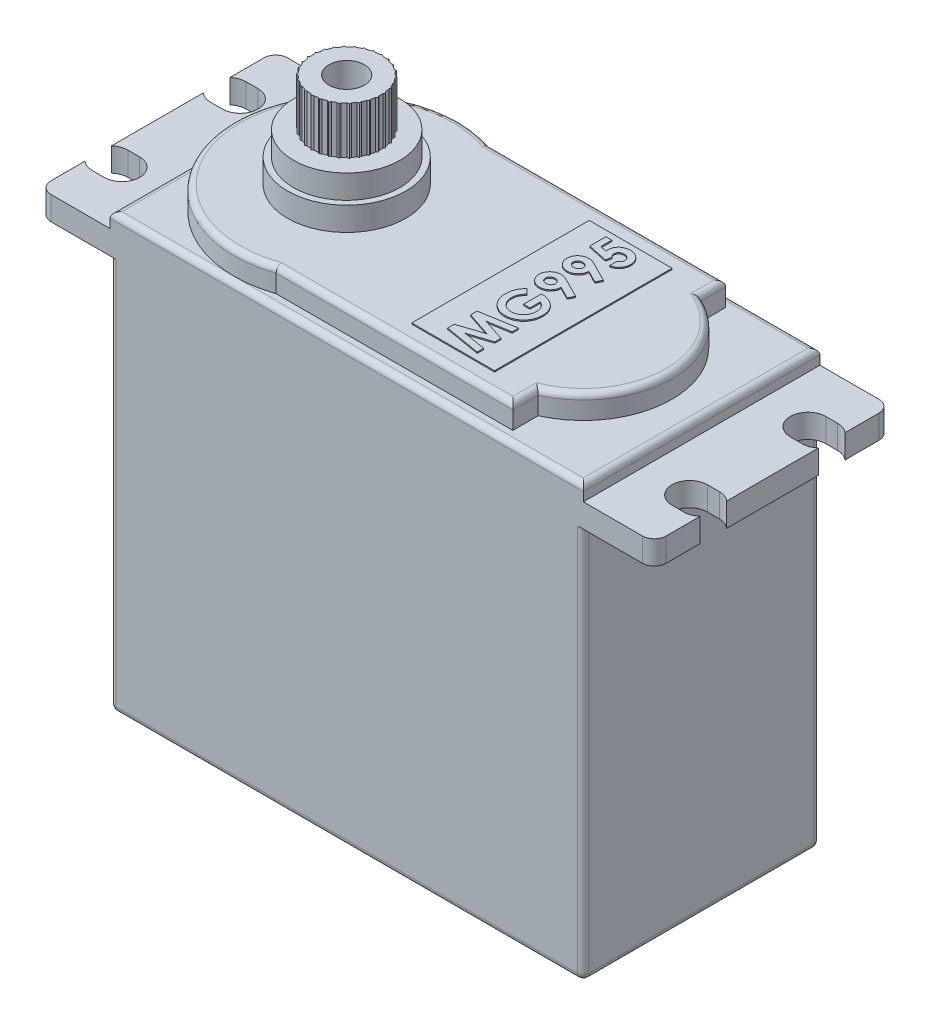
SolidWorks part; units mm, degrees
ref_plane "Front Plane" through (0, 0, 0) normal (0, 0, 1) x (1, 0, 0)
ref_plane "Top Plane" through (0, 0, 0) normal (0, 1, 0) x (1, 0, 0)
ref_plane "Right Plane" through (0, 0, 0) normal (1, 0, 0) x (0, 0, -1)
sketch "Sketch1" plane through (0, 0, 0) normal (0, 1, 0) x (1, 0, 0)
  line L1 (-20, 10) -> (20, 10)
  line L2 (-20, 10) -> (-20, -10)
  line L3 (-20, -10) -> (20, -10)
  line L4 (20, 10) -> (20, -10)
  line L5 (-20, 10) -> (20, -10) construction
  line L6 (-20, -10) -> (20, 10) construction
  point P0 (0, 0)
  dimension "D1" = 20
  dimension "D2" = 40
extrude "Extrude1" add sketch "Sketch1" along normal mid plane 36.5
sketch "Sketch2" plane through (0, 18.25, 0) normal (0, 1, 0) x (1, 0, 0)
  line L0 (13.0414, -6.8557) -> (13.0414, -9)
  line L1 (-6.9586, 9) -> (13.0414, 9)
  line L3 (-6.9586, -9) -> (13.0414, -9)
  line L4 (13.0414, 9) -> (13.0414, 6.8557)
  arc A0 (-6.9586, 9) -> (-6.9586, -9) centre (-10, 0) ccw
  arc A1 (13.0414, -6.8557) -> (13.0414, 6.8557) centre (10, 0) ccw
  dimension "D1" = 19
  dimension "D4" = 15
  dimension "D2" = 10
  dimension "D3" = 18
  dimension "D5" = 20
  dimension "D6" = 10
extrude "Extrude2" add sketch "Sketch2" along normal blind 2
sketch "Sketch3" plane through (0, 20.25, 0) normal (0, 1, 0) x (1, 0, 0)
  circle A0 centre (-10, 0) radius 5
  dimension "D1" = 10
extrude "Extrude3" add sketch "Sketch3" along normal blind 2
sketch "Sketch4" plane through (0, 22.25, 0) normal (0, 1, 0) x (1, 0, 0)
  circle A0 centre (-10, 0) radius 4.5
  dimension "D1" = 9
extrude "Extrude4" add sketch "Sketch4" along normal blind 2
sketch "Sketch5" plane through (0, 24.25, 0) normal (0, 1, 0) x (1, 0, 0)
  line L0 (-10, 0) -> (-10, 3) construction
  line L1 (-10, 3) -> (-10.125, 2.8973)
  line L2 (-10, 3) -> (-9.875, 2.8973)
  line L3 (-9.3763, 2.9344) -> (-9.5199, 2.86)
  line L4 (-9.3763, 2.9344) -> (-9.2753, 2.808)
  line L5 (-8.7798, 2.7406) -> (-8.9358, 2.6977)
  line L6 (-8.7798, 2.7406) -> (-8.7074, 2.596)
  line L7 (-8.2366, 2.4271) -> (-8.3981, 2.4174)
  line L8 (-8.2366, 2.4271) -> (-8.1959, 2.2705)
  line L9 (-7.7706, 2.0074) -> (-7.9305, 2.0316)
  line L10 (-7.7706, 2.0074) -> (-7.7632, 1.8458)
  line L11 (-7.4019, 1.5) -> (-7.5534, 1.5569)
  line L12 (-7.4019, 1.5) -> (-7.4284, 1.3404)
  line L13 (-7.1468, 0.9271) -> (-7.2831, 1.0142)
  line L14 (-7.1468, 0.9271) -> (-7.2059, 0.7764)
  line L15 (-7.0164, 0.3136) -> (-7.1316, 0.4272)
  line L16 (-7.0164, 0.3136) -> (-7.1055, 0.1785)
  line L17 (-7.0164, -0.3136) -> (-7.1055, -0.1785)
  line L18 (-7.0164, -0.3136) -> (-7.1316, -0.4272)
  line L19 (-7.1468, -0.9271) -> (-7.2059, -0.7764)
  line L20 (-7.1468, -0.9271) -> (-7.2831, -1.0142)
  line L21 (-7.4019, -1.5) -> (-7.4284, -1.3404)
  line L22 (-7.4019, -1.5) -> (-7.5534, -1.5569)
  line L23 (-7.7706, -2.0074) -> (-7.7632, -1.8458)
  line L24 (-7.7706, -2.0074) -> (-7.9305, -2.0316)
  line L25 (-8.2366, -2.4271) -> (-8.1959, -2.2705)
  line L26 (-8.2366, -2.4271) -> (-8.3981, -2.4174)
  line L27 (-8.7798, -2.7406) -> (-8.7074, -2.596)
  line L28 (-8.7798, -2.7406) -> (-8.9358, -2.6977)
  line L29 (-9.3763, -2.9344) -> (-9.2753, -2.808)
  line L30 (-9.3763, -2.9344) -> (-9.5199, -2.86)
  line L31 (-10, -3) -> (-9.875, -2.8973)
  line L32 (-10, -3) -> (-10.125, -2.8973)
  line L33 (-10.6237, -2.9344) -> (-10.4801, -2.86)
  line L34 (-10.6237, -2.9344) -> (-10.7247, -2.808)
  line L35 (-11.2202, -2.7406) -> (-11.0642, -2.6977)
  line L36 (-11.2202, -2.7406) -> (-11.2926, -2.596)
  line L37 (-11.7634, -2.4271) -> (-11.6019, -2.4174)
  line L38 (-11.7634, -2.4271) -> (-11.8041, -2.2705)
  line L39 (-12.2294, -2.0074) -> (-12.0695, -2.0316)
  line L40 (-12.2294, -2.0074) -> (-12.2368, -1.8458)
  line L41 (-12.5981, -1.5) -> (-12.4466, -1.5569)
  line L42 (-12.5981, -1.5) -> (-12.5716, -1.3404)
  line L43 (-12.8532, -0.9271) -> (-12.7169, -1.0142)
  line L44 (-12.8532, -0.9271) -> (-12.7941, -0.7764)
  line L45 (-12.9836, -0.3136) -> (-12.8684, -0.4272)
  line L46 (-12.9836, -0.3136) -> (-12.8945, -0.1785)
  line L47 (-12.9836, 0.3136) -> (-12.8945, 0.1785)
  line L48 (-12.9836, 0.3136) -> (-12.8684, 0.4272)
  line L49 (-12.8532, 0.9271) -> (-12.7941, 0.7764)
  line L50 (-12.8532, 0.9271) -> (-12.7169, 1.0142)
  line L51 (-12.5981, 1.5) -> (-12.5716, 1.3404)
  line L52 (-12.5981, 1.5) -> (-12.4466, 1.5569)
  line L53 (-12.2294, 2.0074) -> (-12.2368, 1.8458)
  line L54 (-12.2294, 2.0074) -> (-12.0695, 2.0316)
  line L55 (-11.7634, 2.4271) -> (-11.8041, 2.2705)
  line L56 (-11.7634, 2.4271) -> (-11.6019, 2.4174)
  line L57 (-11.2202, 2.7406) -> (-11.2926, 2.596)
  line L58 (-11.2202, 2.7406) -> (-11.0642, 2.6977)
  line L59 (-10.6237, 2.9344) -> (-10.7247, 2.808)
  line L60 (-10.6237, 2.9344) -> (-10.4801, 2.86)
  arc A0 (-9.875, 2.8973) -> (-10.125, 2.8973) centre (-10, 0) ccw
  circle A1 centre (-10, 0) radius 1.5 construction
  arc A2 (-9.2753, 2.808) -> (-9.5199, 2.86) centre (-10, 0) ccw
  arc A3 (-8.7074, 2.596) -> (-8.9358, 2.6977) centre (-10, 0) ccw
  arc A4 (-8.1959, 2.2705) -> (-8.3981, 2.4174) centre (-10, 0) ccw
  arc A5 (-7.7632, 1.8458) -> (-7.9305, 2.0316) centre (-10, 0) ccw
  arc A6 (-7.4284, 1.3404) -> (-7.5534, 1.5569) centre (-10, 0) ccw
  arc A7 (-7.2059, 0.7764) -> (-7.2831, 1.0142) centre (-10, 0) ccw
  arc A8 (-7.1055, 0.1785) -> (-7.1316, 0.4272) centre (-10, 0) ccw
  arc A9 (-7.1316, -0.4272) -> (-7.1055, -0.1785) centre (-10, 0) ccw
  arc A10 (-7.2831, -1.0142) -> (-7.2059, -0.7764) centre (-10, 0) ccw
  arc A11 (-7.5534, -1.5569) -> (-7.4284, -1.3404) centre (-10, 0) ccw
  arc A12 (-7.9305, -2.0316) -> (-7.7632, -1.8458) centre (-10, 0) ccw
  arc A13 (-8.3981, -2.4174) -> (-8.1959, -2.2705) centre (-10, 0) ccw
  arc A14 (-8.9358, -2.6977) -> (-8.7074, -2.596) centre (-10, 0) ccw
  arc A15 (-9.5199, -2.86) -> (-9.2753, -2.808) centre (-10, 0) ccw
  arc A16 (-10.125, -2.8973) -> (-9.875, -2.8973) centre (-10, 0) ccw
  arc A17 (-10.7247, -2.808) -> (-10.4801, -2.86) centre (-10, 0) ccw
  arc A18 (-11.2926, -2.596) -> (-11.0642, -2.6977) centre (-10, 0) ccw
  arc A19 (-11.8041, -2.2705) -> (-11.6019, -2.4174) centre (-10, 0) ccw
  arc A20 (-12.2368, -1.8458) -> (-12.0695, -2.0316) centre (-10, 0) ccw
  arc A21 (-12.5716, -1.3404) -> (-12.4466, -1.5569) centre (-10, 0) ccw
  arc A22 (-12.7941, -0.7764) -> (-12.7169, -1.0142) centre (-10, 0) ccw
  arc A23 (-12.8945, -0.1785) -> (-12.8684, -0.4272) centre (-10, 0) ccw
  arc A24 (-12.8684, 0.4272) -> (-12.8945, 0.1785) centre (-10, 0) ccw
  arc A25 (-12.7169, 1.0142) -> (-12.7941, 0.7764) centre (-10, 0) ccw
  arc A26 (-12.4466, 1.5569) -> (-12.5716, 1.3404) centre (-10, 0) ccw
  arc A27 (-12.0695, 2.0316) -> (-12.2368, 1.8458) centre (-10, 0) ccw
  arc A28 (-11.6019, 2.4174) -> (-11.8041, 2.2705) centre (-10, 0) ccw
  arc A29 (-11.0642, 2.6977) -> (-11.2926, 2.596) centre (-10, 0) ccw
  arc A30 (-10.4801, 2.86) -> (-10.7247, 2.808) centre (-10, 0) ccw
  dimension "D1" = 5.8
  dimension "D2" = 3
  dimension "D3" = 3
  dimension "D4" = 0.25
extrude "Extrude5" add sketch "Sketch5" along normal blind 4
sketch "Sketch6" plane through (0, 24.25, 0) normal (0, 1, 0) x (1, 0, 0)
  circle A0 centre (-10, 0) radius 2.9
  dimension "D1" = 5.8
extrude "Extrude6" add sketch "Sketch6" along normal blind 4
ref_plane "Plane1" through (0, 15, 0) normal (0, 1, 0) x (-1, 0, 0)
sketch "Sketch7" plane through (0, 15, 0) normal (0, 1, 0) x (-1, 0, 0)
  line L0 (0, 0) -> (0, 15.9425) construction
  line L1 (0, 0) -> (28.4916, 0) construction
  line L2 (20, -10) -> (20, 10) construction
  line L3 (20, 10) -> (26, 10)
  line L4 (20, 10) -> (20, -10)
  line L5 (20, -10) -> (26, -10)
  line L6 (26, 10) -> (26, 6.118)
  line L7 (24, 5) -> (25, 5) construction
  line L8 (24, 3.5) -> (25, 3.5)
  line L9 (24, 6.5) -> (25, 6.5)
  line L10 (24, -5) -> (25, -5) construction
  line L11 (24, -6.5) -> (25, -6.5)
  line L12 (24, -3.5) -> (25, -3.5)
  line L13 (-24, -5) -> (-25, -5) construction
  line L14 (-24, 5) -> (-25, 5) construction
  line L15 (-24, -3.5) -> (-25, -3.5)
  line L16 (-24, -6.5) -> (-25, -6.5)
  line L17 (-24, 6.5) -> (-25, 6.5)
  line L18 (-24, 3.5) -> (-25, 3.5)
  line L19 (-26, 10) -> (-26, 6.118)
  line L20 (-20, -10) -> (-26, -10)
  line L21 (-20, 10) -> (-20, -10)
  line L22 (-20, 10) -> (-26, 10)
  line L23 (26, 3.882) -> (26, -3.882)
  line L24 (26, -6.118) -> (26, -10)
  line L25 (-26, 3.882) -> (-26, -3.882)
  line L26 (-26, -6.118) -> (-26, -10)
  arc A0 (25, 6.5) -> (26, 6.118) centre (25, 5) cw
  arc A1 (24, 6.5) -> (24, 3.5) centre (24, 5) ccw
  arc A2 (24, -6.5) -> (24, -3.5) centre (24, -5) cw
  arc A3 (25, -6.5) -> (26, -6.118) centre (25, -5) ccw
  arc A4 (-25, -6.5) -> (-26, -6.118) centre (-25, -5) cw
  arc A5 (-24, -6.5) -> (-24, -3.5) centre (-24, -5) ccw
  arc A6 (-24, 6.5) -> (-24, 3.5) centre (-24, 5) cw
  arc A7 (-25, 6.5) -> (-26, 6.118) centre (-25, 5) ccw
  arc A8 (26, 3.882) -> (25, 3.5) centre (25, 5) cw
  arc A9 (26, -3.882) -> (25, -3.5) centre (25, -5) ccw
  arc A10 (-26, 3.882) -> (-25, 3.5) centre (-25, 5) ccw
  arc A11 (-26, -3.882) -> (-25, -3.5) centre (-25, -5) cw
  point P1 (24.5, 5)
  dimension "D1" = 24.5
  dimension "D2" = 5
  dimension "D4" = 6
  dimension "D5" = 20
  dimension "D6" = 1
  dimension "D7" = 1.5
extrude "Extrude7" add sketch "Sketch7" along normal blind 2
sketch "Sketch8" plane through (0, 28.25, 0) normal (0, 1, 0) x (1, 0, 0)
  circle A0 centre (-10, 0) radius 1.5
  dimension "D1" = 3
extrude "Extrude8" cut sketch "Sketch8" against normal blind 10
fillet "Fillet4" radius 0.5 6 edges at (17.5, 20.25, 0) (-19.5, 20.25, 0) (3.0414, 20.25, 9) (13.0414, 20.25, -7.9278) (3.0414, 20.25, -9) (13.0414, 20.25, 7.9278)
fillet "Fillet2" radius 0.5 12 edges at (-20, 18.25, 0) (20, 18.25, 0) (0, 18.25, -10) (0, 18.25, 10) (-20, -18.25, 0) (0, -18.25, 10) (20, -18.25, 0) (0, -18.25, -10)
fillet "Fillet3" radius 1 4 edges at (26, 16, 10) (26, 16, -10) (-26, 16, -10) (-26, 16, 10)
sketch "Sketch9" plane through (0, 20.25, 0) normal (0, 1, 0) x (1, 0, 0)
  line L1 (3, 7.5) -> (10, 7.5)
  line L2 (3, 7.5) -> (3, -7.5)
  line L3 (3, -7.5) -> (10, -7.5)
  line L4 (10, 7.5) -> (10, -7.5)
  point P4 (3, 0)
  point P6 (10, 0)
  dimension "D1" = 3
  dimension "D2" = 7
  dimension "D3" = 15
extrude "Extrude9" add sketch "Sketch9" along normal blind 0.1
sketch "Sketch10" plane through (0, 20.35, 0) normal (0, 1, 0) x (1, 0, 0)
  line L0 (8, -8.2) -> (8, 7.5) construction
  text T0 " <b>MG995</b>" font "Century Gothic" height 3
  dimension "D1" = 8
  dimension "D2" = 8.2
extrude "Extrude10" add sketch "Sketch10" along normal blind 0.1
sketch "Sketch12" plane through (0, 18.25, 0) normal (0, 1, 0) x (1, 0, 0)
  circle A0 centre (-10, 0) radius 1.5
  dimension "D1" = 3
extrude "Extrude11" add sketch "Sketch12" against normal blind 37
